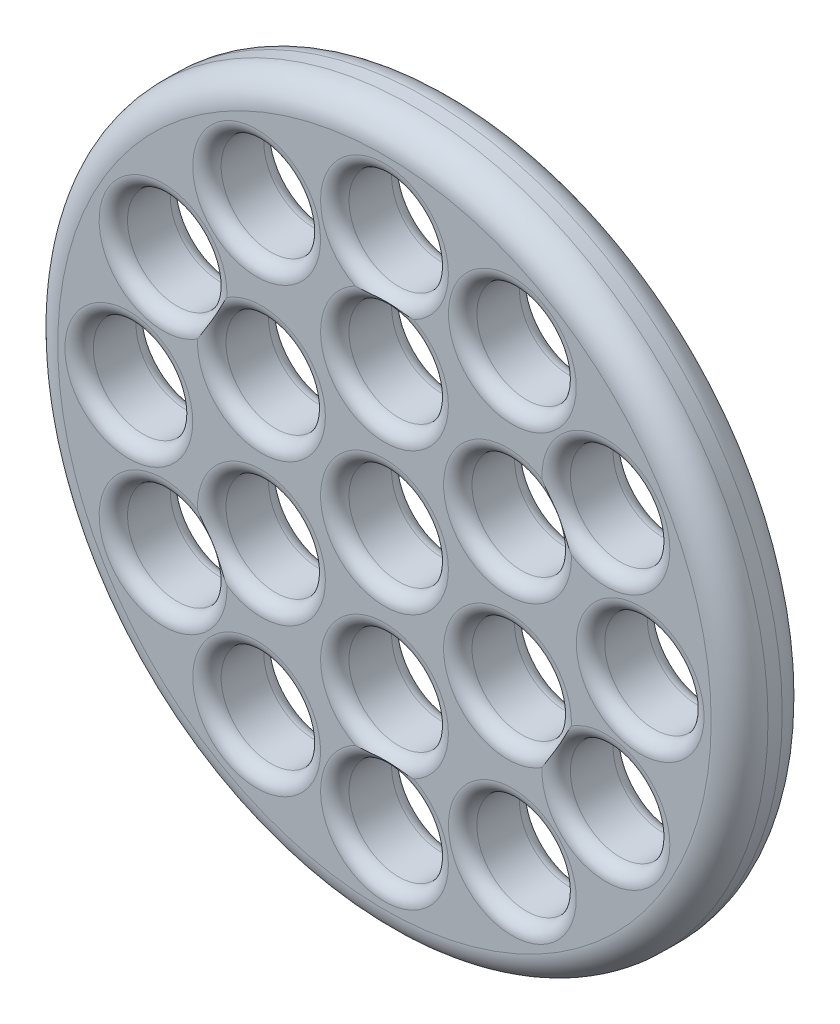
SolidWorks part; units mm, degrees
ref_plane "Front Plane" through (0, 0, 0) normal (0, 0, 1) x (1, 0, 0)
ref_plane "Top Plane" through (0, 0, 0) normal (0, 1, 0) x (1, 0, 0)
ref_plane "Right Plane" through (0, 0, 0) normal (1, 0, 0) x (0, 0, -1)
sketch "Sketch1" plane through (0, 0, 0) normal (0, 0, 1) x (1, 0, 0)
  line L0 (0, 34.4348) -> (0, -34.362) construction
  line L1 (30.2691, 0) -> (-35.0609, 0) construction
  circle A0 centre (0, 0) radius 25
  circle A1 centre (0, 0) radius 3.5
  circle A2 centre (0, 10) radius 3.5
  circle A3 centre (0, 0) radius 22.5
  circle A4 centre (8.6603, 5) radius 3.5
  circle A5 centre (8.6603, -5) radius 3.5
  circle A6 centre (0, -10) radius 3.5
  circle A7 centre (-8.6603, -5) radius 3.5
  circle A8 centre (-8.6603, 5) radius 3.5
  circle A9 centre (-18, 0) radius 3.5
  circle A10 centre (-15.5885, 9) radius 3.5
  circle A11 centre (-9, 15.5885) radius 3.5
  circle A12 centre (0, 18) radius 3.5
  circle A13 centre (9, 15.5885) radius 3.5
  circle A14 centre (15.5885, 9) radius 3.5
  circle A15 centre (18, 0) radius 3.5
  circle A16 centre (15.5885, -9) radius 3.5
  circle A17 centre (9, -15.5885) radius 3.5
  circle A18 centre (0, -18) radius 3.5
  circle A19 centre (-9, -15.5885) radius 3.5
  circle A20 centre (-15.5885, -9) radius 3.5
  point P22 (0, 0)
  point P48 (0, 0)
  dimension "D1" = 50
  dimension "D2" = 7
  dimension "D3" = 7
  dimension "D6" = 7
  dimension "D4" = 10
  dimension "D5" = 6
  dimension "D7" = 18
  dimension "D8" = 12
extrude "Boss-Extrude5" add sketch "Sketch1" along normal blind 5 contours A3 A20 A19 A18 A17 A16 A15 A14 A13 A12 A11 A10 A9 A8 A7 A6 A5 A4 A1 A2 | A0 A3 region at (-24.2929, 0, 0) region at (-21.8636, 0, 0)
fillet "Fillet10" radius 2 2 edges at (25, 0, 0) (25, 0, 5)
fillet "Fillet11" radius 1 38 edges at (3.5, 10, 5) (3.5, 0, 5) (12.1603, 5, 5) (12.1603, -5, 5) (3.5, -10, 5) (-5.1603, -5, 5) (-5.1603, 5, 5) (-14.5, 0, 5) (-12.0885, 9, 5) (-5.5, 15.5885, 5) (3.5, 18, 5) (12.5, 15.5885, 5) (19.0885, 9, 5) (21.5, 0, 5) (19.0885, -9, 5) (12.5, -15.5885, 5) (3.5, -18, 5) (-5.5, -15.5885, 5) (-12.0885, -9, 5) (3.5, 10, 0) (3.5, 0, 0) (12.1603, 5, 0) (12.1603, -5, 0) (3.5, -10, 0) (-5.1603, -5, 0) (-5.1603, 5, 0) (-14.5, 0, 0) (-12.0885, 9, 0) (-5.5, 15.5885, 0) (3.5, 18, 0) (12.5, 15.5885, 0) (19.0885, 9, 0) (21.5, 0, 0) (19.0885, -9, 0) (12.5, -15.5885, 0) (3.5, -18, 0) (-5.5, -15.5885, 0) (-12.0885, -9, 0)
